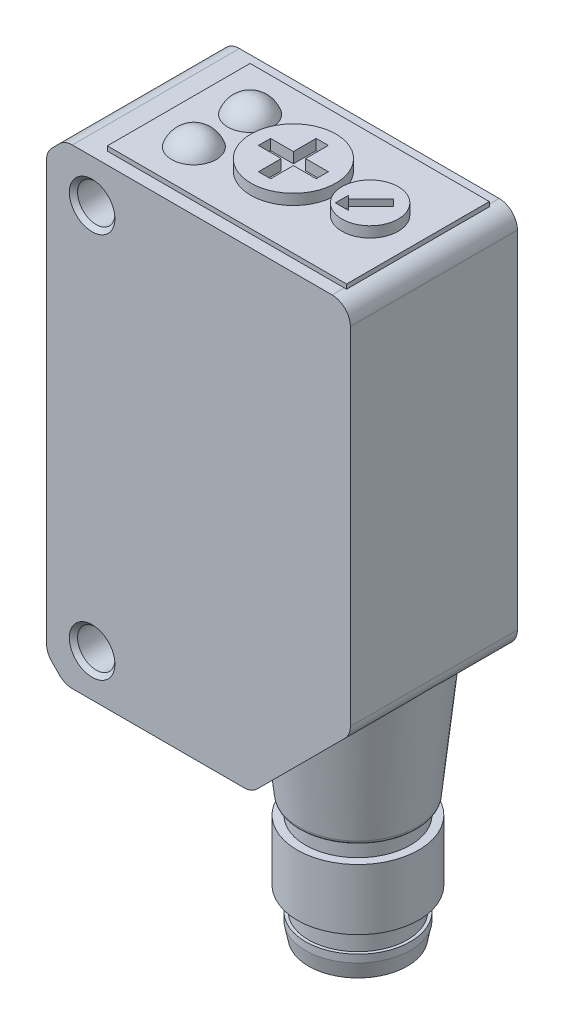
SolidWorks part; units mm, degrees
ref_plane "Front Plane" through (0, 0, 0) normal (0, 0, 1) x (1, 0, 0)
ref_plane "Top Plane" through (0, 0, 0) normal (0, 1, 0) x (1, 0, 0)
ref_plane "Right Plane" through (0, 0, 0) normal (1, 0, 0) x (0, 0, -1)
ref_plane "Plane1" through (0, 0, 0) normal (0, 0, 1) x (1, 0, 0)
sketch "Sketch1" plane through (0, 0, 0) normal (0, 0, 1) x (1, 0, 0)
  line L0 (-3, 26.5029) -> (-3, -1.1029)
  line L1 (-2.6485, -1.9515) -> (-2.1515, -2.4485)
  line L2 (-1.3029, -2.8) -> (10.0029, -2.8)
  line L3 (10.8515, -2.4485) -> (16.6485, 3.3485)
  line L4 (17, 4.1971) -> (17, 27)
  line L5 (15.8, 28.2) -> (-1.3029, 28.2)
  line L6 (-2.1515, 27.8485) -> (-2.6485, 27.3515)
  arc A0 (-3, -1.1029) -> (-2.6485, -1.9515) centre (-1.8, -1.1029) ccw
  arc A1 (-2.1515, -2.4485) -> (-1.3029, -2.8) centre (-1.3029, -1.6) ccw
  arc A2 (10.0029, -2.8) -> (10.8515, -2.4485) centre (10.0029, -1.6) ccw
  arc A3 (16.6485, 3.3485) -> (17, 4.1971) centre (15.8, 4.1971) ccw
  arc A4 (17, 27) -> (15.8, 28.2) centre (15.8, 27) ccw
  arc A5 (-1.3029, 28.2) -> (-2.1515, 27.8485) centre (-1.3029, 27) ccw
  arc A6 (-2.6485, 27.3515) -> (-3, 26.5029) centre (-1.8, 26.5029) ccw
extrude "Boss-Extrude1" add sketch "Sketch1" against normal blind 11
ref_plane "Plane2" through (0, 0, -5.5) normal (0, 0, 1) x (1, 0, 0)
sketch "Sketch2" plane through (0, 0, -5.5) normal (0, 0, 1) x (1, 0, 0)
  line L0 (12, 4.7) -> (16.8991, 4.7)
  line L1 (16.8991, 4.7) -> (15.8973, -4.8314)
  line L2 (15.599, -5.1) -> (15.45, -5.1)
  line L3 (15.45, -5.1) -> (15.45, -6.1)
  line L4 (15.45, -6.1) -> (16, -6.1)
  line L5 (16, -6.1) -> (16, -10.1)
  line L6 (16, -10.1) -> (15.25, -10.1)
  line L7 (15.25, -10.1) -> (15.25, -11.6)
  line L8 (15.25, -11.6) -> (15.45, -11.6)
  line L9 (15.45, -11.6) -> (15.45, -12.1)
  line L10 (15.45, -12.1) -> (15.25, -13.1)
  line L11 (15.25, -13.1) -> (12, -13.1)
  line L12 (12, -13.1) -> (12, 4.7)
  line L13 (12, -13.1) -> (12, 4.7) construction
  arc A0 (15.8973, -4.8314) -> (15.599, -5.1) centre (15.599, -4.8) cw
revolve "Revolve1" add sketch "Sketch2" angle 360 about L13 reverse direction yes
cosmetic thread "Cosmetic Thread1"
ref_plane "Plane3" through (0, -9.3, 0) normal (0, 1, 0) x (1, 0, 0)
sketch "Sketch3" plane through (0, -9.3, 0) normal (0, 1, 0) x (1, 0, 0)
  circle A0 centre (12, 5.5) radius 2.9
  circle A1 centre (13.4158, 4.4714) radius 0.5
  circle A2 centre (13.4158, 6.5286) radius 0.5
  circle A3 centre (11.4592, 3.8357) radius 0.5
  circle A4 centre (11.4592, 7.1643) radius 0.5
extrude "Cut-Extrude1" cut sketch "Sketch3" against normal blind 4
ref_plane "Plane4" through (0, 28.2, 0) normal (0, 1, 0) x (1, 0, 0)
sketch "Sketch4" plane through (0, 28.2, 0) normal (0, 1, 0) x (1, 0, 0)
  line L0 (0.2, 10.2) -> (0.2, 0.8)
  line L1 (0.2, 0.8) -> (15.95, 0.8)
  line L2 (15.95, 0.8) -> (15.95, 10.2)
  line L3 (15.95, 10.2) -> (0.2, 10.2)
  line L4 (11.6565, 4.3565) -> (12.5293, 4.3565)
  line L5 (12.5293, 4.3565) -> (12.305, 4.5808)
  line L6 (12.305, 4.5808) -> (13.7899, 6.0657)
  line L7 (13.7899, 6.0657) -> (13.3657, 6.4899)
  line L8 (13.3657, 6.4899) -> (11.8808, 5.005)
  line L9 (11.8808, 5.005) -> (11.6565, 5.2293)
  line L10 (11.6565, 5.2293) -> (11.6565, 4.3565)
  line L11 (5.85, 5.9) -> (5.85, 5.1)
  line L12 (5.85, 5.1) -> (7.35, 5.1)
  line L13 (7.35, 5.1) -> (7.35, 3.6)
  line L14 (7.35, 3.6) -> (8.15, 3.6)
  line L15 (8.15, 3.6) -> (8.15, 5.1)
  line L16 (8.15, 5.1) -> (9.65, 5.1)
  line L17 (9.65, 5.1) -> (9.65, 5.9)
  line L18 (9.65, 5.9) -> (8.15, 5.9)
  line L19 (8.15, 5.9) -> (8.15, 7.4)
  line L20 (8.15, 7.4) -> (7.35, 7.4)
  line L21 (7.35, 7.4) -> (7.35, 5.9)
  line L22 (7.35, 5.9) -> (5.85, 5.9)
extrude "Boss-Extrude2" add sketch "Sketch4" along normal blind 1
ref_plane "Plane5" through (0, 28.2, 0) normal (0, 1, 0) x (1, 0, 0)
sketch "Sketch5" plane through (0, 28.2, 0) normal (0, 1, 0) x (1, 0, 0)
  line L0 (0.2, 10.2) -> (0.2, 0.8)
  line L1 (0.2, 0.8) -> (15.95, 0.8)
  line L2 (15.95, 0.8) -> (15.95, 10.2)
  line L3 (15.95, 10.2) -> (0.2, 10.2)
  circle A0 centre (12.8, 5.5) radius 1.85
  circle A1 centre (7.75, 5.5) radius 2.8
extrude "Cut-Extrude2" cut sketch "Sketch5" along normal blind 1
ref_plane "Plane6" through (0, 28.2, 0) normal (0, 1, 0) x (1, 0, 0)
sketch "Sketch6" plane through (0, 28.2, 0) normal (0, 1, 0) x (1, 0, 0)
  line L0 (0.2, 10.2) -> (0.2, 0.8)
  line L1 (0.2, 0.8) -> (15.95, 0.8)
  line L2 (15.95, 0.8) -> (15.95, 10.2)
  line L3 (15.95, 10.2) -> (0.2, 10.2)
extrude "Boss-Extrude3" add sketch "Sketch6" along normal blind 0.3
ref_plane "Plane7" through (3.1, 0, 0) normal (1, 0, 0) x (0, 0, -1)
sketch "Sketch7" plane through (3.1, 0, 0) normal (1, 0, 0) x (0, 0, -1)
  line L0 (8.85, 28) -> (5.75, 28)
  line L1 (8.85, 28) -> (5.75, 28) construction
  arc A0 (5.75, 28) -> (8.85, 28) centre (7.3, 28) cw
revolve "Revolve2" add sketch "Sketch7" angle 360 about L1 reverse direction yes
ref_plane "Plane8" through (-2.8, 0, 0) normal (1, 0, 0) x (0, 0, -1)
sketch "Sketch8" plane through (-2.8, 0, 0) normal (1, 0, 0) x (0, 0, -1)
  line L0 (1.425, 19.925) -> (1.425, 2.675)
  line L1 (2.225, 1.875) -> (8.775, 1.875)
  line L2 (9.575, 2.675) -> (9.575, 19.925)
  line L3 (8.775, 20.725) -> (2.225, 20.725)
  arc A0 (1.425, 2.675) -> (2.225, 1.875) centre (2.225, 2.675) ccw
  arc A1 (8.775, 1.875) -> (9.575, 2.675) centre (8.775, 2.675) ccw
  arc A2 (9.575, 19.925) -> (8.775, 20.725) centre (8.775, 19.925) ccw
  arc A3 (2.225, 20.725) -> (1.425, 19.925) centre (2.225, 19.925) ccw
extrude "Cut-Extrude3" cut sketch "Sketch8" against normal blind 0.2
ref_plane "Plane9" through (0, 0, -11) normal (0, 0, 1) x (1, 0, 0)
sketch "Sketch9" plane through (0, 0, -11) normal (0, 0, 1) x (1, 0, 0)
  line L0 (4.4, 0.2) -> (9.0917, 0.2)
  line L1 (9.3745, 0.3172) -> (13.8828, 4.8255)
  line L2 (14, 5.1083) -> (14, 24.8)
  line L3 (13.6, 25.2) -> (4.4, 25.2)
  line L4 (4, 24.8) -> (4, 0.6)
  arc A0 (4, 0.6) -> (4.4, 0.2) centre (4.4, 0.6) ccw
  arc A1 (9.0917, 0.2) -> (9.3745, 0.3172) centre (9.0917, 0.6) ccw
  arc A2 (13.8828, 4.8255) -> (14, 5.1083) centre (13.6, 5.1083) ccw
  arc A3 (14, 24.8) -> (13.6, 25.2) centre (13.6, 24.8) ccw
  arc A4 (4.4, 25.2) -> (4, 24.8) centre (4.4, 24.8) ccw
extrude "Cut-Extrude4" cut sketch "Sketch9" along normal blind 0.1
ref_plane "Plane10" through (0, 0, 0) normal (1, 0, 0) x (0, 0, -1)
sketch "Sketch10" plane through (0, 0, 0) normal (1, 0, 0) x (0, 0, -1)
  line L0 (0, 0) -> (0, 1.5)
  line L1 (0, 1.5) -> (0.2705, 1.2295)
  line L2 (0.2705, 1.2295) -> (10.7295, 1.2295)
  line L3 (10.7295, 1.2295) -> (11, 1.5)
  line L4 (11, 1.5) -> (11, 0)
  line L5 (11, 0) -> (0, 0)
  line L6 (11, 0) -> (0, 0) construction
revolve "Cut-Revolve1" cut sketch "Sketch10" angle 360 about L6 reverse direction yes
cosmetic thread "Cosmetic Thread2"
ref_plane "Plane11" through (0, 0, 0) normal (1, 0, 0) x (0, 0, -1)
sketch "Sketch11" plane through (0, 0, 0) normal (1, 0, 0) x (0, 0, -1)
  line L0 (0, 25.4) -> (0, 26.9)
  line L1 (0, 26.9) -> (0.2705, 26.6295)
  line L2 (0.2705, 26.6295) -> (10.7295, 26.6295)
  line L3 (10.7295, 26.6295) -> (11, 26.9)
  line L4 (11, 26.9) -> (11, 25.4)
  line L5 (11, 25.4) -> (0, 25.4)
  line L6 (11, 25.4) -> (0, 25.4) construction
revolve "Cut-Revolve2" cut sketch "Sketch11" angle 360 about L6 reverse direction yes
cosmetic thread "Cosmetic Thread3"
ref_plane "Plane12" through (3.1, 0, 0) normal (1, 0, 0) x (0, 0, -1)
sketch "Sketch12" plane through (3.1, 0, 0) normal (1, 0, 0) x (0, 0, -1)
  line L0 (5.15, 28) -> (2.05, 28)
  line L1 (5.15, 28) -> (2.05, 28) construction
  arc A0 (2.05, 28) -> (5.15, 28) centre (3.6, 28) cw
revolve "Revolve3" add sketch "Sketch12" angle 360 about L1 reverse direction yes
ref_plane "Plane13" through (0.2, 28.5, -0.8) normal (1, 0, 0) x (0, 0, -1)
